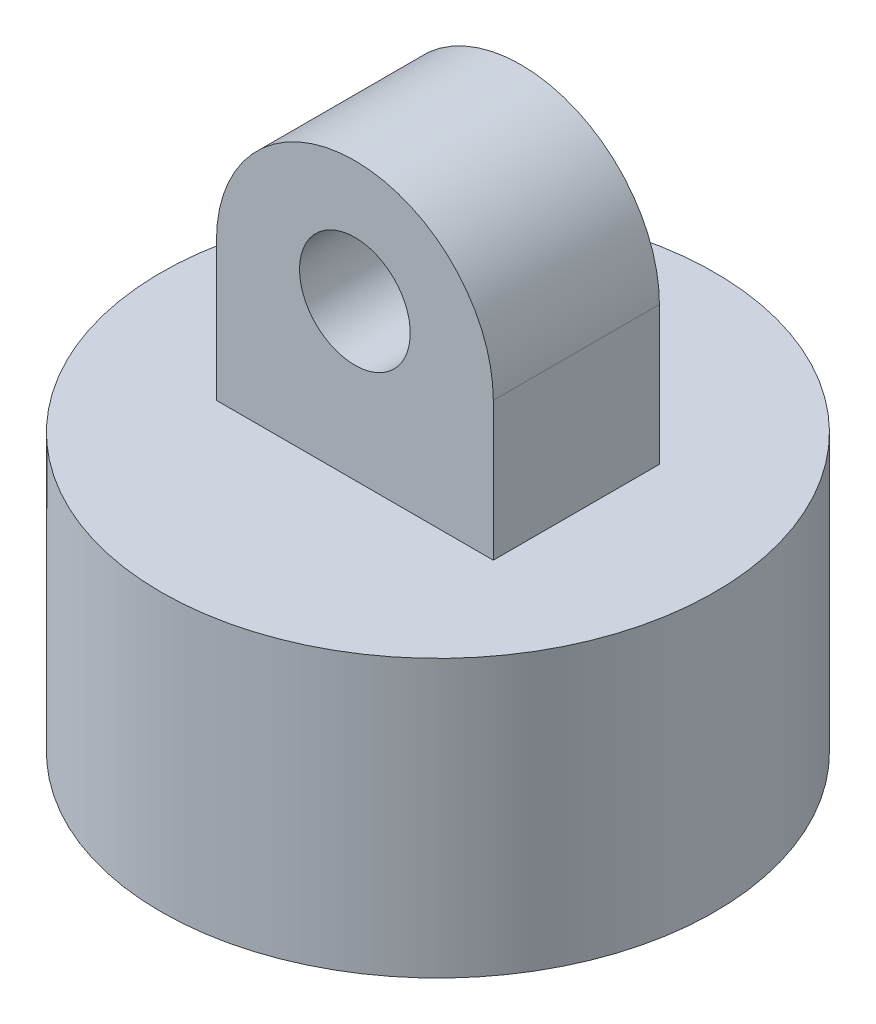
SolidWorks part; units mm, degrees
ref_plane "Alzado" through (0, 0, 0) normal (0, 0, 1) x (1, 0, 0)
ref_plane "Planta" through (0, 0, 0) normal (0, 1, 0) x (1, 0, 0)
ref_plane "Vista lateral" through (0, 0, 0) normal (1, 0, 0) x (0, 0, -1)
sketch "Croquis1" plane through (0, 0, 0) normal (0, 1, 0) x (1, 0, 0)
  circle A0 centre (0, 0) radius 50
  dimension "D1" = 100
extrude "Saliente-Extruir1" add sketch "Croquis1" along normal blind 50
sketch "Croquis2" plane through (0, 50, 0) normal (0, 1, 0) x (1, 0, 0)
  line L0 (-50, 0) -> (50, 0) construction
  line L1 (0, 50) -> (0, -50) construction
  line L3 (-25, 15) -> (25, 15)
  line L4 (-25, 15) -> (-25, -15)
  line L5 (-25, -15) -> (25, -15)
  line L6 (25, 15) -> (25, -15)
  circle A0 centre (0, 0) radius 50 construction
  dimension "D1" = 30
  dimension "D2" = 15
  dimension "D3" = 50
  dimension "D4" = 25
extrude "Saliente-Extruir2" add sketch "Croquis2" along normal blind 50
sketch "Croquis3" plane through (0, 0, -15) normal (0, 0, -1) x (-1, 0, 0)
  line L0 (-25, 100) -> (25, 100) construction
  line L2 (-25, 100) -> (-25, 50) construction
  circle A0 centre (0, 78) radius 10
  point P6 (25, 78.7036)
  dimension "D1" = 20
  dimension "D2" = 22
  dimension "D3" = 25
extrude "Cortar-Extruir1" cut sketch "Croquis3" against normal blind 30
fillet "Redondeo1" 2 edges at (-25, 100, 0) (25, 100, 0) type full round first side face at (-25, 75, 0) second side face at (25, 75, 0) middle face at (0, 100, 0)
